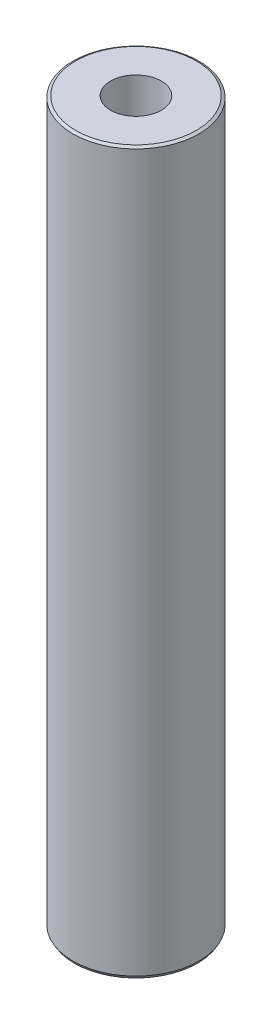
SolidWorks part; units mm, degrees
ref_plane "Front Plane" through (0, 0, 0) normal (0, 0, 1) x (1, 0, 0)
ref_plane "Top Plane" through (0, 0, 0) normal (0, 1, 0) x (1, 0, 0)
ref_plane "Right Plane" through (0, 0, 0) normal (1, 0, 0) x (0, 0, -1)
sketch "Sketch1" plane through (0, 0, 0) normal (0, 1, 0) x (1, 0, 0)
  circle A0 centre (0, 0) radius 52.5
  dimension "SHAFT_OD" = 105
extrude "Boss-Extrude1" add sketch "Sketch1" along normal blind 600
sketch "Sketch2" plane through (0, 0, 0) normal (0, 1, 0) x (1, 0, 0)
  circle A0 centre (0, 0) radius 21.103
  dimension "BORE_D" = 42.206
extrude "Cut-Extrude1" cut sketch "Sketch2" along normal through all
chamfer "Chamfer1" distance 1.3223 angle 60 2 edges at (0, 600, 52.5) (0, 0, 52.5) first distance on face at (0, 600, 52.5) first distance on face at (0, 0, 21.103)
